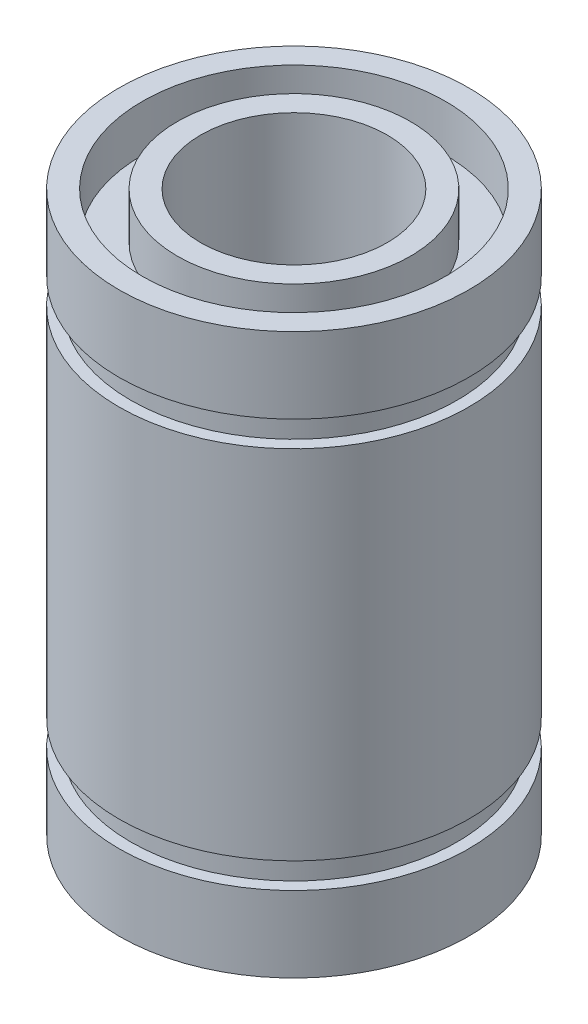
SolidWorks part; units mm, degrees
ref_plane "前基準面" through (0, 0, 0) normal (0, 0, 1) x (1, 0, 0)
ref_plane "上基準面" through (0, 0, 0) normal (0, 1, 0) x (1, 0, 0)
ref_plane "右基準面" through (0, 0, 0) normal (1, 0, 0) x (0, 0, -1)
sketch "草圖1" plane through (0, 0, 0) normal (0, 1, 0) x (1, 0, 0)
  circle A0 centre (0, 0) radius 4000
  circle A1 centre (0, 0) radius 7500
  circle A2 centre (0, 0) radius 6500
  circle A3 centre (0, 0) radius 5000
  dimension "D1" = 8000
  dimension "D2" = 13000
  dimension "D3" = 15000
  dimension "D4" = 10000
extrude "填料-伸長1" add sketch "草圖1" along normal mid plane 24000 contours A1 A2 region at (-7287.868, 0, 0)
extrude "填料-伸長3" add sketch "草圖1<5>" along normal mid plane 24000 separate body contours A3 A0 region at (-4858.5786, 0, 0)
sketch "草圖1<5>" plane through (0, 0, 0) normal (0, 1, 0) x (1, 0, 0) same geometry as "草圖1"
extrude "填料-伸長4" add sketch "草圖1<6>" along normal mid plane 20000 contours A2 A3 region at (-6316.1522, 0, 0)
sketch "草圖1<6>" plane through (0, 0, 0) normal (0, 1, 0) x (1, 0, 0) same geometry as "草圖1"
ref_plane "平面1" through (0, 7650, 0) normal (0, 1, 0) x (1, 0, 0)
ref_plane "平面2" through (0, -7650, 0) normal (0, 1, 0) x (1, 0, 0)
sketch "草圖3" plane through (0, 7650, 0) normal (0, 1, 0) x (1, 0, 0)
  circle A0 centre (0, 0) radius 7000
  circle A1 centre (0, 0) radius 7500
  dimension "D1" = 14000
extrude "除料-伸長1" cut sketch "草圖3" along normal blind 1100
sketch "草圖4" plane through (0, -7650, 0) normal (0, 1, 0) x (1, 0, 0)
  circle A0 centre (0, 0) radius 7500
  circle A1 centre (0, 0) radius 7000
  dimension "D1" = 14000
extrude "除料-伸長2" cut sketch "草圖4" against normal blind 1100
